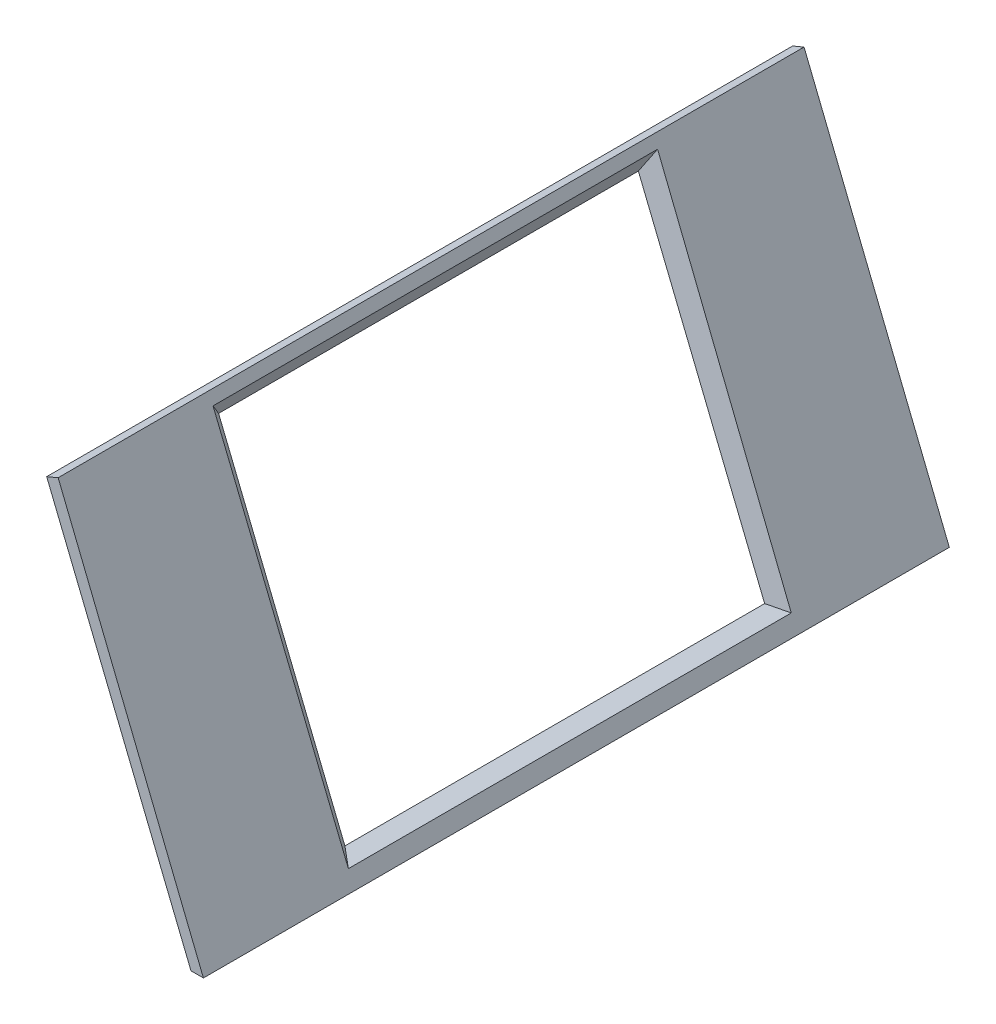
SolidWorks part; units mm, degrees
ref_plane "Plan de face" through (0, 0, 0) normal (0, 0, 1) x (1, 0, 0)
ref_plane "Plan de dessus" through (0, 0, 0) normal (0, 1, 0) x (1, 0, 0)
ref_plane "Plan de droite" through (0, 0, 0) normal (1, 0, 0) x (0, 0, -1)
sketch "Esquisse1" plane through (0, 0, 0) normal (0, 0, 1) x (1, 0, 0)
  line L0 (219.7345, 127.183) -> (103.6557, 413.4004)
  line L1 (103.6557, 413.4004) -> (112.8744, 417.2754)
  line L3 (112.8744, 417.2754) -> (229.7345, 127.183)
  line L4 (229.7345, 127.183) -> (219.7345, 127.183)
  dimension "D1" = 10
extrude "Boss.-Extru.1" add sketch "Esquisse1" along normal blind 600
sketch "Esquisse2" plane through (232.9924, 94.4928, 0) normal (-0.9267, -0.3758, 0) x (0, 0, 1)
  line L1 (131.3037, 324.8619) -> (468.9497, 324.8619)
  line L2 (131.3037, 324.8619) -> (131.3037, 54.5619)
  line L3 (131.3037, 54.5619) -> (468.9497, 54.5619)
  line L4 (468.9497, 324.8619) -> (468.9497, 54.5619)
extrude "Enlèv. mat.-Extru.1" cut sketch "Esquisse2" against normal blind 10 draft 45 draft outward yes
